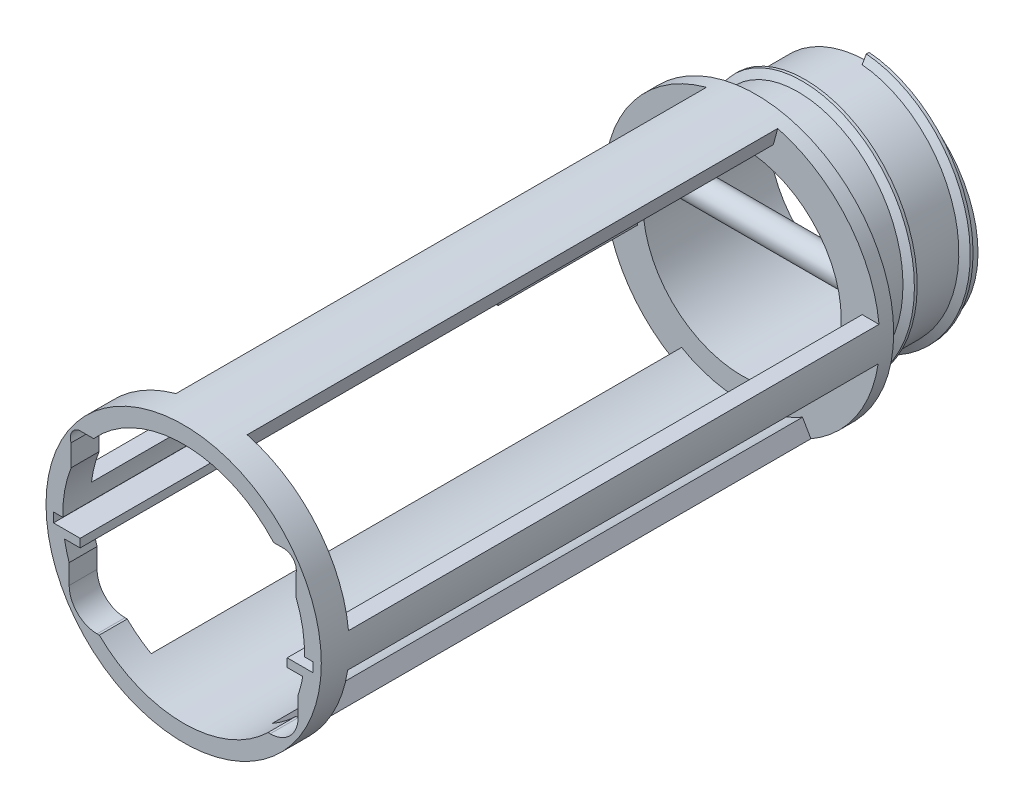
SolidWorks part; units mm, degrees
ref_plane "Front Plane" through (0, 0, 0) normal (0, 0, 1) x (1, 0, 0)
ref_plane "Top Plane" through (0, 0, 0) normal (0, 1, 0) x (1, 0, 0)
ref_plane "Right Plane" through (0, 0, 0) normal (1, 0, 0) x (0, 0, -1)
sketch "Sketch1" plane through (0, 0, 0) normal (0, 0, 1) x (1, 0, 0)
  circle A0 centre (0, 0) radius 19.75
  circle A1 centre (0, 0) radius 17.75
  dimension "D1" = 39.5
  dimension "D2" = 35.5
extrude "Boss-Extrude1" add sketch "Sketch1" along normal blind 20
sketch "Sketch2" plane through (0, 0, 20) normal (0, 0, 1) x (1, 0, 0)
  circle A2 centre (0, 0) radius 17.75 construction
  circle A3 centre (0, 0) radius 17.75
  circle A4 centre (0, 0) radius 24.65
extrude "Boss-Extrude2" add sketch "Sketch2" along normal blind 2.5 separate body
sketch "Sketch15" plane through (0, 0, 22.5) normal (0, 0, 1) x (1, 0, 0)
  circle A0 centre (0, 0) radius 21.65
  circle A1 centre (0, 0) radius 24.65 construction
  circle A2 centre (0, 0) radius 24.65
extrude "Boss-Extrude3" add sketch "Sketch15" along normal blind 100
sketch "Sketch16" plane through (0, 0, 122.5) normal (0, 0, 1) x (1, 0, 0)
  line L1 (-24.5229, -2.5) -> (-21.5052, -2.5)
  line L3 (-24.5229, 2.5) -> (-21.5052, 2.5)
  line L8 (21.5052, 2.5) -> (24.5229, 2.5)
  line L9 (21.5052, -2.5) -> (24.5229, -2.5)
  circle A0 centre (0, 0) radius 24.65 construction
  circle A1 centre (0, 0) radius 21.65 construction
  arc A2 (24.5229, 2.5) -> (-24.5229, 2.5) centre (0, 0) ccw
  arc A3 (21.5052, 2.5) -> (-21.5052, 2.5) centre (0, 0) ccw
  arc A4 (-21.5052, -2.5) -> (21.5052, -2.5) centre (0, 0) ccw
  arc A5 (-24.5229, -2.5) -> (24.5229, -2.5) centre (0, 0) ccw
  point P0 (0, 0)
extrude "Cut-Extrude2" cut sketch "Sketch16" against normal blind 95 from offset 5 offset against normal yes
sketch "Sketch18" plane through (0, 0, 122.5) normal (0, 0, 1) x (1, 0, 0)
  line L26 (-23.3071, -0.506) -> (23.1929, -0.506)
  line L27 (-23.3071, -0.506) -> (-23.3071, -2.206)
  line L28 (-23.3071, -2.206) -> (23.1929, -2.206)
  line L29 (23.1929, -0.506) -> (23.1929, -2.206)
  point P0 (-0.0571, -1.356)
sketch "Sketch19" plane through (0, 0, 122.5) normal (0, 0, 1) x (1, 0, 0)
  line L0 (-12.325, -21.3475) -> (-10.825, -18.7494)
  line L1 (12.325, -21.3475) -> (10.825, -18.7494)
  arc A0 (-12.325, -21.3475) -> (12.325, -21.3475) centre (0, 0) ccw
  circle A2 centre (0, 0) radius 21.65 construction
  arc A3 (-10.825, -18.7494) -> (10.825, -18.7494) centre (0, 0) ccw
extrude "Boss-Extrude5" add sketch "Sketch19" against normal blind 100
extrude "Cut-Extrude6" cut sketch "Sketch18" against normal blind 100
sketch "Sketch22" plane through (0, 0, 122.5) normal (0, 0, 1) x (1, 0, 0)
  line L0 (-21.5373, -2.206) -> (-18.5373, -2.206)
  line L1 (-18.5373, -2.206) -> (-18.5373, -3.706)
  line L2 (-18.5373, -3.706) -> (-21.3304, -3.706)
  line L4 (18.5373, -3.706) -> (21.3304, -3.706)
  line L5 (18.5373, -2.206) -> (18.5373, -3.706)
  line L6 (21.5373, -2.206) -> (18.5373, -2.206)
  arc A1 (-21.5373, -2.206) -> (21.5373, -2.206) centre (0, 0) ccw construction
  arc A2 (-21.5373, -2.206) -> (-21.3304, -3.706) centre (0, 0) ccw
  arc A3 (21.5373, -2.206) -> (21.3304, -3.706) centre (0, 0) cw
extrude "Boss-Extrude11" add sketch "Sketch22" against normal blind 25
sketch "Sketch23" plane through (0, 0, 122.5) normal (0, 0, 1) x (1, 0, 0)
  line L0 (-22.693, -2.206) -> (-18.693, -2.206)
  line L1 (-18.693, -2.206) -> (-18.693, -3.706)
  line L2 (-18.693, -3.706) -> (-22.4968, -3.706)
  line L3 (18.693, -3.706) -> (22.4968, -3.706)
  line L4 (18.693, -2.206) -> (18.693, -3.706)
  line L5 (22.693, -2.206) -> (18.693, -2.206)
  line L7 (18.5373, -2.206) -> (23.1929, -2.206) construction
  arc A0 (-22.693, -2.206) -> (-22.4968, -3.706) centre (0, 0) ccw
  arc A1 (22.693, -2.206) -> (22.4968, -3.706) centre (0, 0) cw
extrude "Boss-Extrude12" add sketch "Sketch23" along normal blind 25 from offset 100 offset against normal yes
sketch "Sketch26" plane through (0, 0, 122.5) normal (0, 0, 1) x (1, 0, 0)
  line L0 (22.4968, -3.706) -> (24.3698, -3.706)
  line L1 (24.3698, -3.706) -> (22.4968, -3.706)
  line L3 (-22.4968, -3.706) -> (-24.3698, -3.706)
  line L5 (18.693, -2.206) -> (23.1929, -2.206) construction
  line L6 (18.693, -2.206) -> (23.1929, -2.206)
  line L7 (23.1929, -2.206) -> (23.1929, -0.506) construction
  line L8 (23.1929, -2.206) -> (23.1929, -0.506)
  line L10 (-23.3071, -2.206) -> (-18.5373, -2.206) construction
  line L11 (23.1929, -0.506) -> (24.6448, -0.506)
  line L12 (-23.3071, -2.206) -> (-18.693, -2.206) construction
  line L13 (-23.3071, -2.206) -> (-22.693, -2.206)
  line L15 (-24.6448, -0.506) -> (-23.3071, -0.506)
  circle A0 centre (0, 0) radius 24.65 construction
  arc A1 (24.3698, -3.706) -> (24.6448, -0.506) centre (0, 0) ccw
  arc A3 (22.4968, -3.706) -> (22.693, -2.206) centre (0, 0) ccw
  arc A4 (-24.6448, -0.506) -> (-24.3698, -3.706) centre (0, 0) ccw
  arc A5 (22.4968, -3.706) -> (22.693, -2.206) centre (0, 0) ccw
  arc A6 (-22.4968, -3.706) -> (-22.693, -2.206) centre (0, 0) cw
  line M5 (23.1929, -2.206) -> (18.5373, -2.206)
  line M11 (-18.5373, -2.206) -> (-23.3071, -2.206)
  line M12 (-23.3071, -2.206) -> (-23.3071, -0.506)
  line M16 (23.1929, -0.506) -> (23.1929, -2.206)
  circle M17 centre (0, 0) radius 24.65
extrude "Boss-Extrude13" add sketch "Sketch26" against normal blind 100 contours L3 A6 L15 M11 M12 M17 | A3 L0 L11 M17 M16 M5 region at (23.7044, -2.2125, 122.5) region at (-23.722, -2.2457, 122.5)
sketch "Sketch27" plane through (0, 0, 0) normal (1, 0, 0) x (0, 0, -1)
  line L1 (-20, -24.65) -> (-20, 24.65) construction
  circle A0 centre (-15, 0) radius 2.3
  dimension "D1" = 5
sketch "Sketch32" plane through (0, 0, 122.5) normal (0, 0, 1) x (1, 0, 0)
  line L1 (-5.6034, 20.9123) -> (-6.3799, 23.8101)
  line L3 (5.6034, 20.9123) -> (6.3799, 23.8101)
  arc A0 (0, 21.65) -> (5.6034, 20.9123) centre (0, 0) cw
  arc A1 (21.6441, -0.506) -> (-21.6441, -0.506) centre (0, 0) ccw construction
  arc A2 (0, 21.65) -> (-5.6034, 20.9123) centre (0, 0) ccw
  circle A3 centre (0, 0) radius 24.65 construction
  arc A4 (6.3799, 23.8101) -> (-6.3799, 23.8101) centre (0, 0) ccw
sketch "Sketch33" plane through (0, 0, 122.5) normal (0, 0, 1) x (1, 0, 0)
  line L2 (-20.5, -10.506) -> (-20.5, -5.506)
  line L3 (15.5, -5.506) -> (-15.5, -5.506)
  line L5 (-15.5, -15.506) -> (15.5, -15.506)
  line L6 (-20.5, -5.506) -> (-15.5, -5.506)
  line L7 (20.5, -10.506) -> (20.5, -5.506)
  line L8 (20.5, -5.506) -> (15.5, -5.506)
  arc A0 (15.5, -15.506) -> (20.5, -10.506) centre (15.5, -10.506) ccw
  arc A5 (-20.5, -10.506) -> (-15.5, -15.506) centre (-15.5, -10.506) ccw
sketch "Sketch34" plane through (0, 0, 122.5) normal (0, 0, 1) x (1, 0, 0)
  line L3 (17.885, 14.4573) -> (-18.652, 14.4573)
  line L4 (-20.15, 11.794) -> (-20.15, 3.0878)
  line L5 (-20.15, 3.0878) -> (20.15, 3.0878)
  line L6 (20.15, 3.0878) -> (20.15, 11.794)
  arc A0 (17.885, 14.4573) -> (20.15, 11.794) centre (17.885, 12.1625) cw
  arc A1 (-18.652, 14.4573) -> (-20.15, 11.794) centre (-18.3358, 12.5266) ccw
  point P0 (0, 3.0878)
extrude "Cut-Extrude12" cut sketch "Sketch33" against normal blind 5
extrude "Cut-Extrude13" cut sketch "Sketch34" against normal blind 5
extrude "Boss-Extrude16" add sketch "Sketch32" against normal up to surface (100 mm away) up to face at (-0.0114, -3.9678, 22.5)
extrude "Boss-Extrude17" add sketch "Sketch27" along normal up to surface and the other way up to surface up to face at (17.75, 0, 20) other way up to face at (17.75, 0, 20)
sketch "Sketch35" plane through (0, 0, 0) normal (0, 0, -1) x (-1, 0, 0)
  circle A0 centre (0, 0) radius 19.75 construction
  circle A1 centre (0, 0) radius 19.75
curve "Helix/Spiral1" pitch 10 height 20 radius 19.75 left hand yes centre (0, 0, 0) axis (0, 0, 1) start towards (0, 1, 0)
sketch "Sketch36" plane through (0, 0, 0) normal (1, 0, 0) x (0, 0, -1)
  line L0 (-1, 19.75) -> (-0.25, 21.049)
  line L1 (-1, 19.75) -> (1, 19.75)
  line L2 (-0.25, 21.049) -> (0.25, 21.049)
  line L3 (0.25, 21.049) -> (1, 19.75)
  point P4 (0, 19.75)
  dimension "D1" = 60
  dimension "D2" = 60
  dimension "D3" = 2
  dimension "D4" = 0.5
sweep "Sweep1" add profiles "Sketch36" path "Helix/Spiral1"
